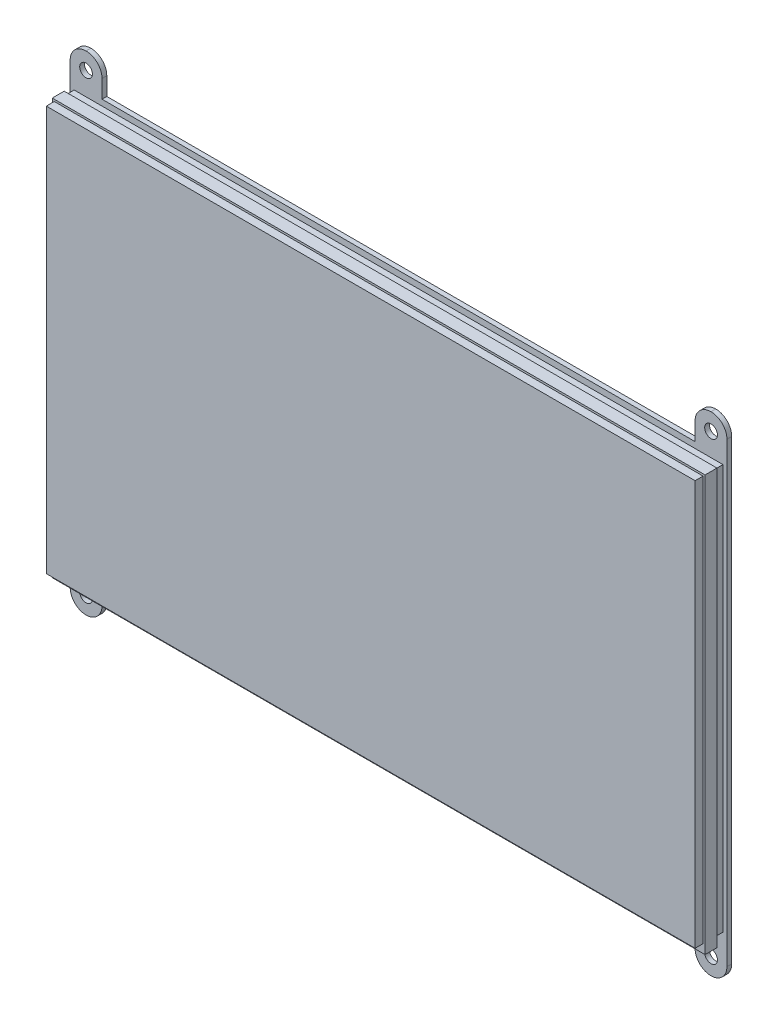
SolidWorks part; units mm, degrees
material "Alliage 2018"
ref_plane "Plan de face" through (0, 0, 0) normal (0, 0, 1) x (1, 0, 0)
ref_plane "Plan de dessus" through (0, 0, 0) normal (0, 1, 0) x (1, 0, 0)
ref_plane "Plan de droite" through (0, 0, 0) normal (1, 0, 0) x (0, 0, -1)
sketch "Esquisse1" plane through (0, 0, 0) normal (0, 0, 1) x (1, 0, 0)
  line L0 (0, 58.5) -> (0, -58.5) construction
  line L1 (-74.5, 52.865) -> (74.5, 52.865)
  line L2 (-82.5, 57.375) -> (-82.5, -57.375)
  line L3 (-74.5, -52.865) -> (74.5, -52.865)
  line L5 (-82.5, 64.135) -> (82.5, -64.135) construction
  line L6 (-82.5, -64.135) -> (82.5, 64.135) construction
  line L7 (-82, 51.865) -> (82, 51.865)
  line L8 (-82, 51.865) -> (-82, -50.865)
  line L9 (-82, -50.865) -> (82, -50.865)
  line L10 (82, 51.865) -> (82, -50.865)
  line L11 (82.5, -57.375) -> (82.5, 57.375)
  line L13 (-78.51, 61.365) -> (-78.49, 61.365)
  line L14 (-74.5, 52.865) -> (-74.5, 57.375)
  line L15 (82.5, 0) -> (-82.5, 0) construction
  line L16 (74.5, 52.865) -> (74.5, 57.375)
  line L17 (78.51, 61.365) -> (78.49, 61.365)
  line L19 (-81.5, -50.365) -> (81.5, -50.365)
  line L20 (-81.5, -50.365) -> (-81.5, 51.365)
  line L22 (78.51, -61.365) -> (78.49, -61.365)
  line L23 (74.5, -52.865) -> (74.5, -57.375)
  line L24 (-74.5, -52.865) -> (-74.5, -57.375)
  line L25 (-78.51, -61.365) -> (-78.49, -61.365)
  line L27 (-81.5, 51.365) -> (81.5, 51.365)
  line L28 (81.5, -50.365) -> (81.5, 51.365)
  circle A0 centre (-78.51, 57.115) radius 1.6
  arc A1 (-78.49, 61.365) -> (-74.5, 57.375) centre (-78.49, 57.375) cw
  arc A2 (-82.5, 57.375) -> (-78.51, 61.365) centre (-78.51, 57.375) cw
  arc A3 (82.5, 57.375) -> (78.51, 61.365) centre (78.51, 57.375) ccw
  arc A4 (78.49, 61.365) -> (74.5, 57.375) centre (78.49, 57.375) ccw
  circle A5 centre (78.51, 57.115) radius 1.6
  circle A6 centre (78.51, -57.115) radius 1.6
  arc A7 (78.49, -61.365) -> (74.5, -57.375) centre (78.49, -57.375) cw
  arc A8 (82.5, -57.375) -> (78.51, -61.365) centre (78.51, -57.375) cw
  arc A9 (-82.5, -57.375) -> (-78.51, -61.365) centre (-78.51, -57.375) ccw
  arc A10 (-78.49, -61.365) -> (-74.5, -57.375) centre (-78.49, -57.375) ccw
  circle A11 centre (-78.51, -57.115) radius 1.6
  point P0 (0, 0)
  point P21 (-74.5, 61.365)
  point P24 (-82.5, 61.365)
  point P34 (82.5, 61.365)
  point P35 (74.5, 61.365)
  point P45 (74.5, -61.365)
  point P46 (82.5, -61.365)
  point P56 (-82.5, -61.365)
  point P57 (-74.5, -61.365)
  dimension "D5" = 4.25
  dimension "D6" = 3.99
  dimension "D2" = 165
  dimension "D3" = 8
  dimension "D4" = 114.75
  dimension "D7" = 1
  dimension "D8" = 2
  dimension "D11" = 0.5
  dimension "D12" = 0.5
  dimension "D13" = 0.5
  dimension "D14" = 0.5
extrude "Boss.-Extru.1" add sketch "Esquisse1" against normal blind 1.2 contours A0 | L14 A1 L13 A2 L2 A9 L25 A10 L24 L3 L23 A7 L22 A8 L11 A3 L17 A4 L16 L1 | A5 | A6 | A11 region at (-78.51, 57.115, 0)
extrude "Boss.-Extru.2" add sketch "Esquisse1<3>" along normal blind 2 contours L27 L28 L19 L20
sketch "Esquisse1<3>" plane through (0, 0, 0) normal (0, 0, 1) x (1, 0, 0) same geometry as "Esquisse1"
sketch "Esquisse3" plane through (0, 0, 2) normal (0, 0, 1) x (1, 0, 0)
  line L0 (-82, 51.865) -> (82, 51.865) construction
  line L1 (-82, 51.865) -> (82, 51.865)
  line L2 (-82, 51.865) -> (-82, -52.5)
  line L3 (-82, -52.5) -> (82, -52.5)
  line L4 (82, 51.865) -> (82, -52.5)
  line L5 (82, 51.865) -> (82, -50.865) construction
  line L7 (-82, 51.865) -> (-82, -50.865) construction
  dimension "D1" = 0
  dimension "D2" = 0
  dimension "D3" = 0
extrude "Boss.-Extru.4" add sketch "Esquisse3" along normal blind 3
sketch "Esquisse4" plane through (0, 0, 5) normal (0, 0, 1) x (1, 0, 0)
  line L1 (-81.5, 51.365) -> (81.5, 51.365)
  line L2 (-81.5, 51.365) -> (-81.5, -50.365)
  line L3 (-81.5, -50.365) -> (81.5, -50.365)
  line L4 (81.5, 51.365) -> (81.5, -50.365)
extrude "Boss.-Extru.5" add sketch "Esquisse4" along normal blind 2
sketch "Esquisse5" plane through (0, 0, -1.2) normal (0, 0, -1) x (-1, 0, 0)
  line L0 (0, 58.5) -> (0, -58.5) construction
  line L1 (-18.75, -28.365) -> (18.75, -28.365)
  line L2 (-18.75, -28.365) -> (-18.75, -33.365)
  line L3 (-18.75, -33.365) -> (18.75, -33.365)
  line L4 (18.75, -28.365) -> (18.75, -33.365)
  line L5 (-18.75, -28.365) -> (18.75, -33.365) construction
  line L6 (-18.75, -33.365) -> (18.75, -28.365) construction
  line L7 (74.5, -52.865) -> (-74.5, -52.865) construction
  line L9 (-60, 12.635) -> (-55, 12.635)
  line L10 (-60, 12.635) -> (-60, 10.635)
  line L11 (-60, 10.635) -> (-55, 10.635)
  line L12 (-55, 12.635) -> (-55, 10.635)
  point P0 (0, -30.865)
  point P17 (-95.4352, 22.7961)
  dimension "D1" = 37.5
  dimension "D2" = 5
  dimension "D3" = 19.5
  dimension "D4" = 63.5
  dimension "D5" = 2
  dimension "D7" = 5
extrude "Enlèv. mat.-Extru.1" cut sketch "Esquisse5" against normal blind 1.2
sketch "Esquisse6" plane through (0, 0, -1.2) normal (0, 0, -1) x (-1, 0, 0)
  line L0 (18.75, -33.365) -> (82.5, -33.365) construction
  text T0 "7inch HDMI Display-C" font "Century Gothic" height in points 14
extrude "Enlèv. mat.-Extru.2" cut sketch "Esquisse6" against normal blind 0.1
sketch "Esquisse7" plane through (0, 0, -1.2) normal (0, 0, -1) x (-1, 0, 0)
  line L0 (76.75, -38.365) -> (18.75, -38.365) construction
  line L2 (-18.75, -33.365) -> (18.75, -33.365) construction
  text T0 "1024 x 600 pixel" font "Century Gothic" height in points 10
  dimension "D1" = 5
  dimension "D2" = 58
extrude "Enlèv. mat.-Extru.3" cut sketch "Esquisse7" against normal blind 0.1
